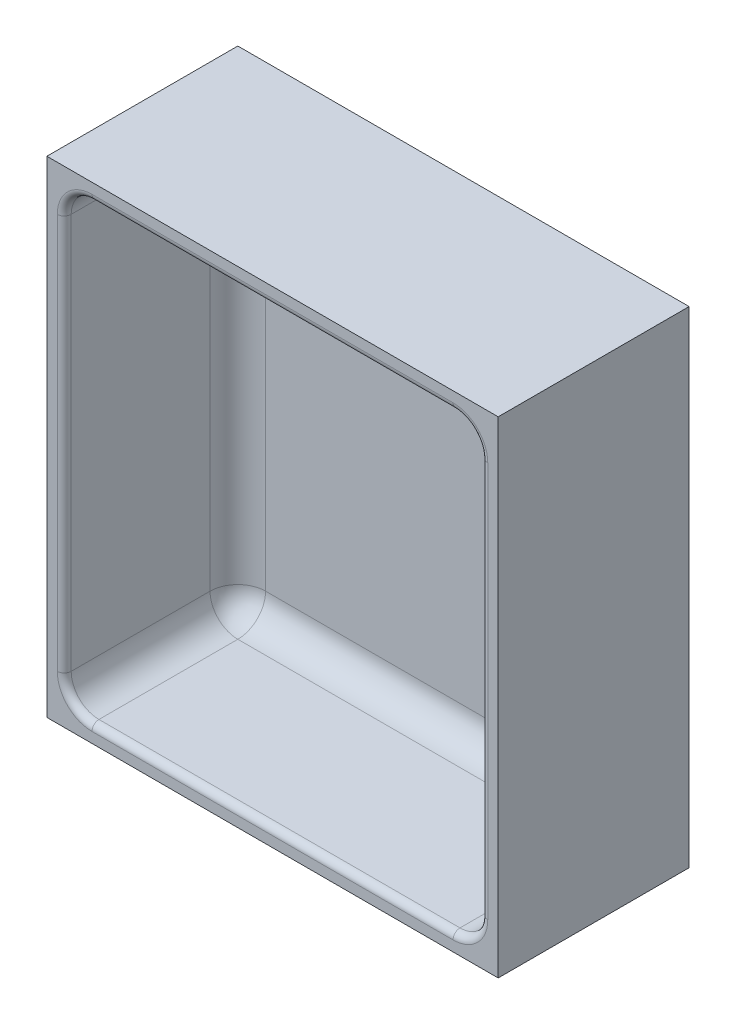
SolidWorks part; units mm, degrees
ref_plane "Ön Düzlem" through (0, 0, 0) normal (1, 0, 0) x (0, 1, 0)
ref_plane "Üst Düzlem" through (0, 0, 0) normal (0, 0, 1) x (0, 1, 0)
ref_plane "Sağ Düzlem" through (0, 0, 0) normal (0, 1, 0) x (-1, 0, 0)
sketch "Çizim1" plane through (0, 0, 0) normal (0, 0, 1) x (0, 1, 0)
  line L0 (0, 0) -> (140, 0)
  line L1 (0, 0) -> (0, 130)
  line L2 (0, 130) -> (140, 130)
  line L3 (140, 130) -> (140, 0)
  line L4 (5, 5) -> (5, 125)
  line L5 (5, 125) -> (135, 125)
  line L6 (135, 125) -> (135, 5)
  line L7 (5, 5) -> (135, 5)
  dimension "D1" = 5
extrude "Yükseklik-Ekstrüzyon1" add sketch "Çizim1" along normal blind 5 contours L4 L5 L6 L7
extrude "Yükseklik-Ekstrüzyon2" add sketch "Çizim1<3>" along normal blind 55
sketch "Çizim1<3>" plane through (0, 0, 0) normal (0, 0, 1) x (0, 1, 0) same geometry as "Çizim1"
fillet "Radyus1" radius 8 8 edges at (-5, 135, 30) (-125, 135, 30) (-125, 5, 30) (-5, 5, 30) (-5, 70, 5) (-65, 135, 5) (-125, 70, 5) (-65, 5, 5)
fillet "Radyus2" radius 2 8 edges at (-122.6569, 7.3431, 55) (-125, 70, 55) (-122.6569, 132.6569, 55) (-65, 135, 55) (-7.3431, 132.6569, 55) (-5, 70, 55) (-7.3431, 7.3431, 55) (-65, 5, 55)
